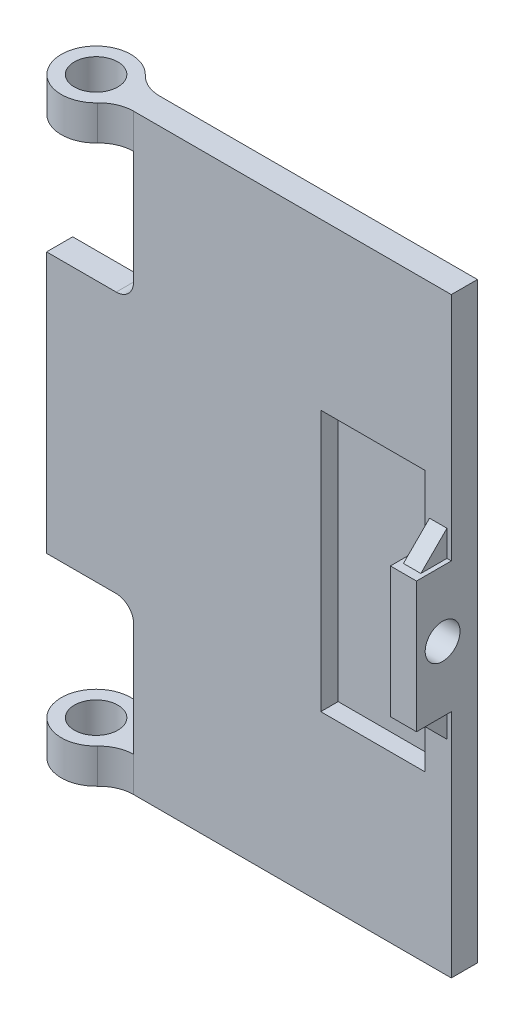
SolidWorks part; units mm, degrees
ref_plane "前视基准面" through (0, 0, 0) normal (0, 0, 1) x (1, 0, 0)
ref_plane "上视基准面" through (0, 0, 0) normal (0, 1, 0) x (1, 0, 0)
ref_plane "右视基准面" through (0, 0, 0) normal (1, 0, 0) x (0, 0, -1)
sketch "草图1" plane through (0, 0, 0) normal (0, 0, 1) x (1, 0, 0)
  line L1 (-18.25, 34) -> (18.25, 34)
  line L2 (-18.25, 34) -> (-18.25, -34)
  line L3 (-18.25, -34) -> (18.25, -34)
  line L4 (18.25, 34) -> (18.25, -34)
  line L5 (0, -34) -> (0, 34) construction
  line L6 (-18.25, 0) -> (18.25, 0) construction
  point P0 (0, 0)
  dimension "D1" = 68
  dimension "D2" = 36.5
extrude "凸台-拉伸1" add sketch "草图1" along normal blind 3
sketch "草图2" plane through (0, -34, 0) normal (0, -1, 0) x (1, 0, 0)
  line L0 (-18.25, 3) -> (-18.25, 0) construction
  line L1 (-18.25, 1.5) -> (-16.0565, 1.5) construction
  line L2 (-18.25, 3) -> (18.25, 3) construction
  line L4 (-18.25, 3) -> (-18.25, 0)
  arc A0 (-21.1547, 4.25) -> (-21.1547, -1.25) centre (-24.0595, 1.5) ccw
  arc A1 (-21.1547, 4.25) -> (-18.25, 3) centre (-18.25, 7) ccw
  arc A2 (-21.1547, -1.25) -> (-18.25, 0) centre (-18.25, -4) cw
  circle A3 centre (-24.0595, 1.5) radius 2.5
  point P1 (-28.0595, 1.5)
  point P5 (-18.25, 1.5)
  point P18 (-28.0595, 1.5)
  dimension "D1" = 4
  dimension "D2" = 8
  dimension "D3" = 5
extrude "凸台-拉伸2" add sketch "草图2" against normal blind 4
sketch "草图3" plane through (0, 34, 0) normal (0, 1, 0) x (1, 0, 0)
  line L1 (-18.25, -3) -> (-18.25, 0)
  line L2 (-18.25, -3) -> (-18.25, 0)
  arc A3 (-18.25, -3) -> (-21.1547, -4.25) centre (-18.25, -7) ccw
  arc A4 (-21.1547, 1.25) -> (-18.25, 0) centre (-18.25, 4) ccw
  arc A5 (-21.1547, 1.25) -> (-21.1547, -4.25) centre (-24.0595, -1.5) ccw
  arc A6 (-18.25, -3) -> (-21.1547, -4.25) centre (-18.25, -7) ccw
  arc A7 (-21.1547, 1.25) -> (-18.25, 0) centre (-18.25, 4) ccw
  arc A8 (-21.1547, 1.25) -> (-21.1547, -4.25) centre (-24.0595, -1.5) ccw
  dimension "D1" = 0
extrude "凸台-拉伸3" add sketch "草图3" against normal blind 4
sketch "草图4" plane through (0, 34, 0) normal (0, 1, 0) x (1, 0, 0)
  circle A0 centre (-24.0595, -1.5) radius 2.5
  dimension "D1" = 5
extrude "切除-拉伸1" cut sketch "草图4" against normal blind 4
sketch "草图7" plane through (0, 0, 3) normal (0, 0, 1) x (1, 0, 0)
  line L0 (18.25, -34) -> (18.25, 34) construction
  line L1 (15.25, 7.5) -> (18.25, 7.5)
  line L2 (15.25, 7.5) -> (15.25, -7.5)
  line L3 (15.25, -7.5) -> (18.25, -7.5)
  line L4 (18.25, 7.5) -> (18.25, -7.5)
  line L5 (16.75, -7.5) -> (16.75, 7.5) construction
  line L6 (15.25, 0) -> (18.25, 0) construction
  point P0 (16.75, 0)
  dimension "D1" = 3
  dimension "D2" = 15
extrude "凸台-拉伸4" add sketch "草图7" along normal blind 4
sketch "草图8" plane through (0, 0, 3) normal (0, 0, 1) x (1, 0, 0)
  line L0 (15.25, 7.5) -> (15.25, 15)
  line L1 (15.25, 15) -> (3.25, 15)
  line L2 (3.25, 15) -> (3.25, -15)
  line L3 (0, 0) -> (-6.9848, 0) construction
  line L4 (15.25, -15) -> (3.25, -15)
  line L5 (15.25, -7.5) -> (15.25, -15)
  line L6 (15.25, 7.5) -> (15.25, -7.5)
  point P9 (3.25, 0)
  dimension "D1" = 30
  dimension "D2" = 12
extrude "切除-拉伸2" cut sketch "草图8" against normal blind 2
sketch "草图9" plane through (18.25, 0, 0) normal (1, 0, 0) x (0, 0, -1)
  line L0 (-7, -7.5) -> (-7, 7.5) construction
  circle A0 centre (-4, 0) radius 2
  dimension "D1" = 4
  dimension "D2" = 3
extrude "切除-拉伸3" cut sketch "草图9" against normal blind 5
ref_plane "基准面1" through (16.75, 0, 0) normal (1, 0, 0) x (0, 0, -1)
sketch "草图10" plane through (16.75, 0, 0) normal (1, 0, 0) x (0, 0, -1)
  line L0 (-6, -7.5) -> (-3, -10.5)
  line L1 (-7, -7.5) -> (-3, -7.5) construction
  line L2 (-3, -34) -> (-3, -7.5) construction
  line L3 (-3, -10.5) -> (-3, -7.5)
  line L4 (-3, -7.5) -> (-6, -7.5)
  dimension "D1" = 3
extrude "凸台-拉伸5" add sketch "草图10" along normal mid plane 2
mirror "镜向1" about plane through (0, 0, 0) normal (0, 1, 0) of "凸台-拉伸5"
sketch "草图11" plane through (0, 0, 3) normal (0, 0, 1) x (1, 0, 0)
  line L0 (-18.25, 30) -> (-18.25, -30) construction
  line L1 (-18.25, 15) -> (-28.25, 15)
  line L2 (-18.25, 15) -> (-18.25, -15)
  line L3 (-18.25, -15) -> (-28.25, -15)
  line L4 (-28.25, 15) -> (-28.25, -15)
  point P6 (-28.25, 0)
  dimension "D1" = 30
  dimension "D2" = 10
extrude "凸台-拉伸6" add sketch "草图11" against normal blind 3
fillet "圆角1" radius 2 2 edges at (-18.25, -15, 1.5) (-18.25, 15, 1.5)
fillet "圆角2" radius 1 1 edges at (15.25, 0, 1)
